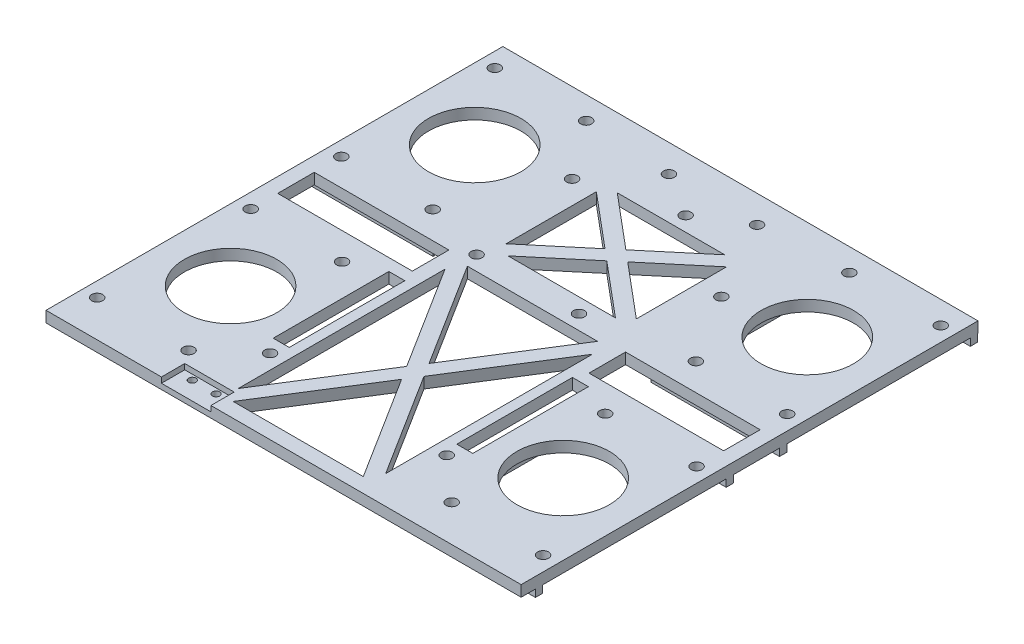
SolidWorks part; units mm, degrees
ref_plane "Front Plane" through (0, 0, 0) normal (0, 0, 1) x (1, 0, 0)
ref_plane "Top Plane" through (0, 0, 0) normal (0, 1, 0) x (1, 0, 0)
ref_plane "Right Plane" through (0, 0, 0) normal (1, 0, 0) x (0, 0, -1)
sketch "Sketch1" plane through (0, 0, 0) normal (0, 1, 0) x (1, 0, 0)
  line L1 (-65, 62.5) -> (65, 62.5)
  line L2 (-65, 62.5) -> (-65, -62.5)
  line L3 (-65, -62.5) -> (65, -62.5)
  line L4 (65, 62.5) -> (65, -62.5)
  line L5 (-65, 62.5) -> (65, -62.5) construction
  line L6 (-65, -62.5) -> (65, 62.5) construction
  point P0 (0, 0)
  dimension "D1" = 130
  dimension "D2" = 125
extrude "Boss-Extrude1" add sketch "Sketch1" along normal blind 5
sketch "Sketch2" plane through (0, 5, 0) normal (0, 1, 0) x (1, 0, 0)
  line L1 (-65, -62.5) -> (65, -62.5) construction
  line L2 (-65, 62.5) -> (-65, -62.5) construction
  circle A0 centre (-61, -52.5) radius 1.5
  circle A1 centre (-36, -52.5) radius 1.5
  circle A2 centre (-36, -10.5) radius 1.5
  circle A3 centre (-61, -10.5) radius 1.5
  circle A4 centre (-45.5, -31.5) radius 12.65
  dimension "D2" = 25.3
  dimension "D7" = 3
  dimension "D8" = 3
  dimension "D9" = 3
  dimension "D10" = 3
  dimension "D1" = 19.5
  dimension "D3" = 31
  dimension "D4" = 4
  dimension "D5" = 10
  dimension "D6" = 10
  dimension "D11" = 4
  dimension "D12" = 42
  dimension "D13" = 42
  dimension "D14" = 25
  dimension "D15" = 25
extrude "Cut-Extrude1" cut sketch "Sketch2" against normal blind 10
ref_plane "Plane1" through (0, 0, 0) normal (-1, 0, 0) x (0, 0, 1)
ref_plane "Plane2" through (0, 0, 0) normal (0, 0, 1) x (1, 0, 0)
mirror "Mirror3" about plane through (0, 0, 0) normal (-1, 0, 0) of "Cut-Extrude1"
sketch "Sketch4" plane through (0, 5, 0) normal (0, 1, 0) x (1, 0, 0)
  line L0 (0, 62.5) -> (0, 47.5) construction
  line L1 (65, 62.5) -> (-65, 62.5) construction
  line L2 (-12.0498, 55) -> (12.0498, 55) construction
  circle A0 centre (0, 47.5) radius 1.5
  circle A1 centre (12.0498, 55) radius 1.5
  circle A2 centre (-12.0498, 55) radius 1.5
  point P9 (0, 55)
  dimension "D2" = 3
  dimension "D3" = 3
  dimension "D4" = 3
  dimension "D1" = 15
  dimension "D5" = 24.0996
extrude "Cut-Extrude3" cut sketch "Sketch4" against normal blind 10
sketch "Sketch5" plane through (0, 0, 0) normal (0, -1, 0) x (1, 0, 0)
  line L0 (-58.15, 31.5) -> (-65, 31.5) construction
  line L1 (-65, -62.5) -> (-65, 62.5) construction
  line L2 (-65, 56.6) -> (-65, 6.4)
  line L3 (-65, 56.6) -> (-31.8, 56.6)
  line L4 (-31.8, 56.6) -> (-31.8, 6.4)
  line L5 (-31.8, 6.4) -> (-65, 6.4)
  line L6 (-65, 58.6) -> (-29.8, 58.6)
  line L7 (-29.8, 58.6) -> (-29.8, 4.4)
  line L8 (-29.8, 4.4) -> (-65, 4.4)
  line L9 (-65, 4.4) -> (-65, 6.4)
  line L10 (-65, 58.6) -> (-65, 56.6)
  circle A0 centre (-45.5, 31.5) radius 12.65 construction
  point P10 (-65, 31.5)
  line M39 (-65, 62.5) -> (-65, -62.5)
  dimension "D1" = 50.2
  dimension "D2" = 33.2
  dimension "D3" = 2
  dimension "D4" = 2
  dimension "D5" = 2
extrude "Boss-Extrude2" add sketch "Sketch5" along normal blind 2 contours L8 L7 L6 L3 L4 L5 M39 region at (-64.3537, 0, 57.6)
mirror "Mirror5" about plane through (0, 0, 0) normal (-1, 0, 0) of "Boss-Extrude2"
ref_plane "Plane3" through (0, 0, 0) normal (0, 0, 1) x (1, 0, 0)
ref_plane "Plane4" through (0, 0, -1.9) normal (0, 0, 1) x (1, 0, 0)
mirror "Mirror7" about plane through (0, 0, -1.9) normal (0, 0, 1) of "Mirror5", "Boss-Extrude2", "Mirror3"
ref_plane "Plane5" through (0, 0, 0) normal (0, -1, 0) x (-1, 0, 0)
sketch "Sketch10" plane through (0, 0, 0) normal (0, -1, 0) x (-1, 0, 0)
  circle A0 centre (-24.17, -42.03) radius 1.5
  circle A1 centre (24.17, -42.03) radius 1.5
  circle A2 centre (-8.73, 9.6) radius 1.5
  circle A3 centre (19.29, 9.6) radius 1.5
  circle A4 centre (-24.17, 33.11) radius 1.5
  circle A5 centre (24.17, 40.6) radius 1.5
  dimension "D1" = 3
  dimension "D6" = 3
  dimension "D7" = 3
  dimension "D10" = 3
  dimension "D11" = 3
  dimension "D12" = 3
extrude "Cut-Extrude8" cut sketch "Sketch10" against normal through all
sketch "Sketch11" plane through (0, 0, 0) normal (0, -1, 0) x (1, 0, 0)
  circle A0 centre (-12.0498, -55) radius 2.65
  circle A1 centre (0, -47.5) radius 2.65
  circle A2 centre (12.0498, -55) radius 2.65
  circle A3 centre (-24.17, -40.6) radius 2.65
  circle A4 centre (24.17, -33.11) radius 2.65
  circle A5 centre (8.73, -9.6) radius 2.65
  circle A6 centre (-19.29, -9.6) radius 2.65
  circle A7 centre (-24.17, 42.03) radius 2.65
  circle A8 centre (24.17, 42.03) radius 2.65
  circle A9 centre (-61, -14.3) radius 2.65
  circle A10 centre (-36, -14.3) radius 2.65
  circle A11 centre (-61, -56.3) radius 2.65
  circle A12 centre (-36, -56.3) radius 2.65
  circle A13 centre (36, -56.3) radius 2.65
  circle A14 centre (61, -56.3) radius 2.65
  circle A15 centre (36, -14.3) radius 2.65
  circle A16 centre (61, -14.3) radius 2.65
  circle A17 centre (36, 10.5) radius 2.65
  circle A18 centre (61, 10.5) radius 2.65
  circle A19 centre (61, 52.5) radius 2.65
  circle A20 centre (36, 52.5) radius 2.65
  circle A21 centre (-36, 52.5) radius 2.65
  circle A22 centre (-36, 10.5) radius 2.65
  circle A23 centre (-61, 10.5) radius 2.65
  circle A24 centre (-61, 52.5) radius 2.65
  dimension "D1" = 5.3
  dimension "D2" = 5.3
  dimension "D3" = 5.3
  dimension "D4" = 5.3
  dimension "D5" = 5.3
  dimension "D6" = 5.3
  dimension "D7" = 5.3
  dimension "D8" = 5.3
  dimension "D9" = 5.3
  dimension "D10" = 5.3
  dimension "D11" = 5.3
  dimension "D12" = 5.3
  dimension "D13" = 5.3
  dimension "D14" = 5.3
  dimension "D15" = 5.3
  dimension "D16" = 5.3
  dimension "D17" = 5.3
  dimension "D18" = 5.3
  dimension "D19" = 5.3
  dimension "D20" = 5.3
  dimension "D21" = 5.3
  dimension "D22" = 5.3
  dimension "D23" = 5.3
  dimension "D24" = 5.3
  dimension "D25" = 5.3
extrude "Cut-Extrude9" cut sketch "Sketch11" against normal blind 0.5
sketch "Sketch12" plane through (0, 5, 0) normal (0, 1, 0) x (1, 0, 0)
  line L0 (-65, -62.5) -> (65, -62.5) construction
  line L1 (-20.17, 5.6) -> (20.17, 5.6)
  line L2 (-20.17, 5.6) -> (-20.17, -58.5)
  line L3 (-20.17, -58.5) -> (20.17, -58.5)
  line L4 (20.17, 5.6) -> (20.17, -58.5)
  line L5 (-20.17, 5.6) -> (20.17, -58.5) construction
  line L6 (-20.17, -58.5) -> (20.17, 5.6) construction
  line L7 (-17.8069, 5.6) -> (0, -22.6951)
  line L8 (20.17, -54.7451) -> (2.3631, -26.45)
  line L9 (2.3631, -26.45) -> (20.17, 1.8451)
  line L10 (0, -22.6951) -> (17.8069, 5.6)
  line L11 (-20.17, 1.8451) -> (-2.3631, -26.45)
  line L12 (-2.3631, -26.45) -> (-20.17, -54.7451)
  line L13 (-17.8069, -58.5) -> (0, -30.2049)
  line L14 (0, -30.2049) -> (17.8069, -58.5)
  circle A0 centre (-19.29, 9.6) radius 1.5 construction
  circle A1 centre (-24.17, -42.03) radius 1.5 construction
  circle A2 centre (24.17, -42.03) radius 1.5 construction
  dimension "D2" = 4
  dimension "D3" = 4
  dimension "D1" = 4
  dimension "D4" = 4
  dimension "D5" = 2
  dimension "D6" = 2
  dimension "D7" = 2
  dimension "D8" = 2
extrude "Cut-Extrude10" cut sketch "Sketch12" against normal through all contours L12 L11 L2 | L7 L10 L1 | L9 L8 L4 | L14 L13 L3 region at (0, 5, 3.8317) region at (-14.2344, 5, 26.45) region at (14.2344, 5, 26.45) region at (0, 5, 49.0683)
sketch "Sketch13" plane through (0, 5, 0) normal (0, 1, 0) x (1, 0, 0)
  line L0 (-61, 14.3) -> (-61, -10.5) construction
  line L1 (-61, 1.9) -> (-61, -3.1)
  line L2 (-61, -3.1) -> (-24.17, -3.1)
  line L3 (-24.17, -3.1) -> (-24.17, 6.9)
  line L4 (-24.17, 6.9) -> (-61, 6.9)
  line L5 (-61, 6.9) -> (-61, 1.9)
  line L6 (-20.17, 1.8451) -> (-20.17, -54.7451) construction
  dimension "D1" = 10
  dimension "D2" = 5
  dimension "D3" = 4
extrude "Cut-Extrude11" cut sketch "Sketch13" against normal through all
mirror "Mirror9" about plane through (0, 0, 0) normal (-1, 0, 0) of "Cut-Extrude11"
sketch "Sketch14" plane through (0, 5, 0) normal (0, 1, 0) x (1, 0, 0)
  line L0 (-17.8069, 43.5) -> (17.8069, 13.6) construction
  line L1 (-17.8069, 43.5) -> (17.8069, 43.5)
  line L2 (-17.8069, 43.5) -> (-17.8069, 13.6)
  line L3 (-17.8069, 13.6) -> (17.8069, 13.6)
  line L4 (17.8069, 43.5) -> (17.8069, 13.6)
  line L5 (-17.8069, 13.6) -> (17.8069, 43.5) construction
  line L6 (-17.8069, 40.8886) -> (-3.1104, 28.55)
  line L7 (-3.1104, 28.55) -> (-17.8069, 16.2114)
  line L8 (-14.6965, 13.6) -> (0, 25.9386)
  line L9 (0, 25.9386) -> (14.6965, 13.6)
  line L10 (17.8069, 16.2114) -> (3.1104, 28.55)
  line L11 (3.1104, 28.55) -> (17.8069, 40.8886)
  line L12 (14.6965, 43.5) -> (0, 31.1614)
  line L13 (0, 31.1614) -> (-14.6965, 43.5)
  circle A0 centre (0, 47.5) radius 1.5 construction
  circle A1 centre (8.73, 9.6) radius 1.5 construction
  dimension "D1" = 4
  dimension "D2" = 4
  dimension "D3" = 2
  dimension "D4" = 2
  dimension "D5" = 2
  dimension "D6" = 2
  dimension "D7" = 2
  dimension "D8" = 2
  dimension "D9" = 2
  dimension "D10" = 2
extrude "Cut-Extrude12" cut sketch "Sketch14" against normal through all contours L7 L6 L2 | L13 L12 L1 | L11 L10 L4 | L9 L8 L3 region at (0, 5, -39.3871) region at (-12.9081, 5, -28.55) region at (12.9081, 5, -28.55) region at (0, 5, -17.7129)
sketch "Sketch15" plane through (0, 5, 0) normal (0, 1, 0) x (1, 0, 0)
  line L1 (-63.5, 58.8) -> (-58.5, 58.8)
  line L2 (-63.5, 58.8) -> (-63.5, 53.8)
  line L3 (-63.5, 53.8) -> (-58.5, 53.8)
  line L4 (65, -62.5) -> (65, 62.5)
  line L5 (65, 62.5) -> (-65, 62.5)
  line L6 (-65, 62.5) -> (-65, -62.5)
  line L7 (-65, -62.5) -> (65, -62.5)
  line L8 (65, -62.5) -> (65, 62.5)
  line L9 (65, 62.5) -> (-65, 62.5)
  line L10 (-65, 62.5) -> (-65, -62.5)
  line L11 (-65, -62.5) -> (65, -62.5)
  line L12 (-58.5, 58.8) -> (-58.5, 53.8)
  line L13 (-63.5, 58.8) -> (-58.5, 53.8) construction
  line L14 (-63.5, 53.8) -> (-58.5, 58.8) construction
  line L15 (-38.5, 58.8) -> (-33.5, 58.8)
  line L16 (-38.5, 58.8) -> (-38.5, 53.8)
  line L17 (-38.5, 53.8) -> (-33.5, 53.8)
  line L18 (-33.5, 58.8) -> (-33.5, 53.8)
  line L19 (-38.5, 58.8) -> (-33.5, 53.8) construction
  line L20 (-38.5, 53.8) -> (-33.5, 58.8) construction
  line L21 (-14.5498, 57.5) -> (-9.5498, 57.5)
  line L22 (-14.5498, 57.5) -> (-14.5498, 52.5)
  line L23 (-14.5498, 52.5) -> (-9.5498, 52.5)
  line L24 (-9.5498, 57.5) -> (-9.5498, 52.5)
  line L25 (-14.5498, 57.5) -> (-9.5498, 52.5) construction
  line L26 (-14.5498, 52.5) -> (-9.5498, 57.5) construction
  line L27 (-2.5, 50) -> (2.5, 50)
  line L28 (-2.5, 50) -> (-2.5, 45)
  line L29 (-2.5, 45) -> (2.5, 45)
  line L30 (2.5, 50) -> (2.5, 45)
  line L31 (-2.5, 50) -> (2.5, 45) construction
  line L32 (-2.5, 45) -> (2.5, 50) construction
  line L33 (9.5498, 57.5) -> (14.5498, 57.5)
  line L34 (9.5498, 57.5) -> (9.5498, 52.5)
  line L35 (9.5498, 52.5) -> (14.5498, 52.5)
  line L36 (14.5498, 57.5) -> (14.5498, 52.5)
  line L37 (9.5498, 57.5) -> (14.5498, 52.5) construction
  line L38 (9.5498, 52.5) -> (14.5498, 57.5) construction
  line L39 (33.5, 58.8) -> (38.5, 58.8)
  line L40 (33.5, 58.8) -> (33.5, 53.8)
  line L41 (33.5, 53.8) -> (38.5, 53.8)
  line L42 (38.5, 58.8) -> (38.5, 53.8)
  line L43 (33.5, 58.8) -> (38.5, 53.8) construction
  line L44 (33.5, 53.8) -> (38.5, 58.8) construction
  line L45 (63.5, 58.8) -> (58.5, 58.8)
  line L46 (63.5, 58.8) -> (63.5, 53.8)
  line L47 (63.5, 53.8) -> (58.5, 53.8)
  line L48 (58.5, 58.8) -> (58.5, 53.8)
  line L49 (63.5, 58.8) -> (58.5, 53.8) construction
  line L50 (63.5, 53.8) -> (58.5, 58.8) construction
  line L51 (33.5, 16.8) -> (38.5, 16.8)
  line L52 (33.5, 16.8) -> (33.5, 11.8)
  line L53 (33.5, 11.8) -> (38.5, 11.8)
  line L54 (38.5, 16.8) -> (38.5, 11.8)
  line L55 (33.5, 16.8) -> (38.5, 11.8) construction
  line L56 (33.5, 11.8) -> (38.5, 16.8) construction
  line L57 (63.5, 16.8) -> (58.5, 16.8)
  line L58 (63.5, 16.8) -> (63.5, 11.8)
  line L59 (63.5, 11.8) -> (58.5, 11.8)
  line L60 (58.5, 16.8) -> (58.5, 11.8)
  line L61 (63.5, 16.8) -> (58.5, 11.8) construction
  line L62 (63.5, 11.8) -> (58.5, 16.8) construction
  line L63 (21.67, 35.61) -> (26.67, 35.61)
  line L64 (21.67, 35.61) -> (21.67, 30.61)
  line L65 (21.67, 30.61) -> (26.67, 30.61)
  line L66 (26.67, 35.61) -> (26.67, 30.61)
  line L67 (21.67, 35.61) -> (26.67, 30.61) construction
  line L68 (21.67, 30.61) -> (26.67, 35.61) construction
  line L69 (33.5, -8) -> (38.5, -8)
  line L70 (33.5, -8) -> (33.5, -13)
  line L71 (33.5, -13) -> (38.5, -13)
  line L72 (38.5, -8) -> (38.5, -13)
  line L73 (33.5, -8) -> (38.5, -13) construction
  line L74 (33.5, -13) -> (38.5, -8) construction
  line L75 (63.5, -8) -> (58.5, -8)
  line L76 (63.5, -8) -> (63.5, -13)
  line L77 (63.5, -13) -> (58.5, -13)
  line L78 (58.5, -8) -> (58.5, -13)
  line L79 (63.5, -8) -> (58.5, -13) construction
  line L80 (63.5, -13) -> (58.5, -8) construction
  line L81 (21.67, -39.53) -> (26.67, -39.53)
  line L82 (21.67, -39.53) -> (21.67, -44.53)
  line L83 (21.67, -44.53) -> (26.67, -44.53)
  line L84 (26.67, -39.53) -> (26.67, -44.53)
  line L85 (21.67, -39.53) -> (26.67, -44.53) construction
  line L86 (21.67, -44.53) -> (26.67, -39.53) construction
  line L87 (38.5, -50) -> (33.5, -50)
  line L88 (38.5, -50) -> (38.5, -55)
  line L89 (38.5, -55) -> (33.5, -55)
  line L90 (33.5, -50) -> (33.5, -55)
  line L91 (38.5, -50) -> (33.5, -55) construction
  line L92 (38.5, -55) -> (33.5, -50) construction
  line L93 (63.5, -50) -> (58.5, -50)
  line L94 (63.5, -50) -> (63.5, -55)
  line L95 (63.5, -55) -> (58.5, -55)
  line L96 (58.5, -50) -> (58.5, -55)
  line L97 (63.5, -50) -> (58.5, -55) construction
  line L98 (63.5, -55) -> (58.5, -50) construction
  line L99 (-26.67, -39.53) -> (-21.67, -39.53)
  line L100 (-26.67, -39.53) -> (-26.67, -44.53)
  line L101 (-26.67, -44.53) -> (-21.67, -44.53)
  line L102 (-21.67, -39.53) -> (-21.67, -44.53)
  line L103 (-26.67, -39.53) -> (-21.67, -44.53) construction
  line L104 (-26.67, -44.53) -> (-21.67, -39.53) construction
  line L105 (-38.5, -50) -> (-33.5, -50)
  line L106 (-38.5, -50) -> (-38.5, -55)
  line L107 (-38.5, -55) -> (-33.5, -55)
  line L108 (-33.5, -50) -> (-33.5, -55)
  line L109 (-38.5, -50) -> (-33.5, -55) construction
  line L110 (-38.5, -55) -> (-33.5, -50) construction
  line L111 (-38.5, -8) -> (-33.5, -8)
  line L112 (-38.5, -8) -> (-38.5, -13)
  line L113 (-38.5, -13) -> (-33.5, -13)
  line L114 (-33.5, -8) -> (-33.5, -13)
  line L115 (-38.5, -8) -> (-33.5, -13) construction
  line L116 (-38.5, -13) -> (-33.5, -8) construction
  line L117 (6.23, 12.1) -> (11.23, 12.1)
  line L118 (6.23, 12.1) -> (6.23, 7.1)
  line L119 (6.23, 7.1) -> (11.23, 7.1)
  line L120 (11.23, 12.1) -> (11.23, 7.1)
  line L121 (6.23, 12.1) -> (11.23, 7.1) construction
  line L122 (6.23, 7.1) -> (11.23, 12.1) construction
  line L123 (-21.79, 12.1) -> (-16.79, 12.1)
  line L124 (-21.79, 12.1) -> (-21.79, 7.1)
  line L125 (-21.79, 7.1) -> (-16.79, 7.1)
  line L126 (-16.79, 12.1) -> (-16.79, 7.1)
  line L127 (-21.79, 12.1) -> (-16.79, 7.1) construction
  line L128 (-21.79, 7.1) -> (-16.79, 12.1) construction
  line L129 (-26.67, 43.1) -> (-21.67, 43.1)
  line L130 (-26.67, 43.1) -> (-26.67, 38.1)
  line L131 (-26.67, 38.1) -> (-21.67, 38.1)
  line L132 (-21.67, 43.1) -> (-21.67, 38.1)
  line L133 (-26.67, 43.1) -> (-21.67, 38.1) construction
  line L134 (-26.67, 38.1) -> (-21.67, 43.1) construction
  line L135 (-63.5, 16.8) -> (-58.5, 16.8)
  line L136 (-63.5, 16.8) -> (-63.5, 11.8)
  line L137 (-63.5, 11.8) -> (-58.5, 11.8)
  line L138 (-58.5, 16.8) -> (-58.5, 11.8)
  line L139 (-63.5, 16.8) -> (-58.5, 11.8) construction
  line L140 (-63.5, 11.8) -> (-58.5, 16.8) construction
  line L141 (-38.5, 16.8) -> (-33.5, 16.8)
  line L142 (-38.5, 16.8) -> (-38.5, 11.8)
  line L143 (-38.5, 11.8) -> (-33.5, 11.8)
  line L144 (-33.5, 16.8) -> (-33.5, 11.8)
  line L145 (-38.5, 16.8) -> (-33.5, 11.8) construction
  line L146 (-38.5, 11.8) -> (-33.5, 16.8) construction
  line L147 (-63.5, -8) -> (-58.5, -8)
  line L148 (-63.5, -8) -> (-63.5, -13)
  line L149 (-63.5, -13) -> (-58.5, -13)
  line L150 (-58.5, -8) -> (-58.5, -13)
  line L151 (-63.5, -8) -> (-58.5, -13) construction
  line L152 (-63.5, -13) -> (-58.5, -8) construction
  line L153 (-63.5, -50) -> (-58.5, -50)
  line L154 (-63.5, -50) -> (-63.5, -55)
  line L155 (-63.5, -55) -> (-58.5, -55)
  line L156 (-58.5, -50) -> (-58.5, -55)
  line L157 (-63.5, -50) -> (-58.5, -55) construction
  line L158 (-63.5, -55) -> (-58.5, -50) construction
  circle A0 centre (-61, 56.3) radius 1.5 construction
  circle A1 centre (-36, 56.3) radius 1.5 construction
  circle A2 centre (-12.0498, 55) radius 1.5 construction
  circle A3 centre (0, 47.5) radius 1.5 construction
  circle A4 centre (12.0498, 55) radius 1.5 construction
  circle A5 centre (36, 56.3) radius 1.5 construction
  circle A6 centre (61, 56.3) radius 1.5 construction
  circle A7 centre (24.17, 33.11) radius 1.5 construction
  circle A8 centre (36, 14.3) radius 1.5 construction
  circle A9 centre (61, 14.3) radius 1.5 construction
  circle A10 centre (-24.17, 40.6) radius 1.5 construction
  circle A11 centre (-61, 14.3) radius 1.5 construction
  circle A12 centre (-36, 14.3) radius 1.5 construction
  circle A13 centre (-19.29, 9.6) radius 1.5 construction
  circle A14 centre (8.73, 9.6) radius 1.5 construction
  circle A15 centre (-61, -10.5) radius 1.5 construction
  circle A16 centre (-36, -10.5) radius 1.5 construction
  circle A17 centre (36, -10.5) radius 1.5 construction
  circle A18 centre (61, -10.5) radius 1.5 construction
  circle A19 centre (61, -52.5) radius 1.5 construction
  circle A20 centre (36, -52.5) radius 1.5 construction
  circle A21 centre (24.17, -42.03) radius 1.5 construction
  circle A22 centre (-24.17, -42.03) radius 1.5 construction
  circle A23 centre (-36, -52.5) radius 1.5 construction
  circle A24 centre (-61, -52.5) radius 1.5 construction
  point P2 (-61, 56.3)
  point P12 (-36, 56.3)
  point P20 (-12.0498, 55)
  point P26 (0, 47.5)
  point P32 (12.0498, 55)
  point P38 (36, 56.3)
  point P44 (61, 56.3)
  point P50 (36, 14.3)
  point P56 (61, 14.3)
  point P62 (24.17, 33.11)
  point P84 (36, -10.5)
  point P90 (61, -10.5)
  point P96 (24.17, -42.03)
  point P102 (36, -52.5)
  point P108 (61, -52.5)
  point P114 (-24.17, -42.03)
  point P120 (-36, -52.5)
  point P126 (-36, -10.5)
  point P132 (8.73, 9.6)
  point P138 (-19.29, 9.6)
  point P144 (-24.17, 40.6)
  point P150 (-61, 14.3)
  point P156 (-36, 14.3)
  point P162 (-61, -10.5)
  point P168 (-61, -52.5)
  dimension "D2" = 2.5
  dimension "D3" = 2.5
  dimension "D4" = 2.5
  dimension "D5" = 2.5
  dimension "D6" = 2.5
  dimension "D7" = 2.5
  dimension "D8" = 2.5
  dimension "D9" = 2.5
  dimension "D10" = 2.5
  dimension "D11" = 2.5
  dimension "D12" = 2.5
  dimension "D13" = 2.5
  dimension "D15" = 2.5
  dimension "D16" = 2.5
  dimension "D17" = 2.5
  dimension "D18" = 2.5
  dimension "D19" = 2.5
  dimension "D20" = 2.5
  dimension "D21" = 2.5
  dimension "D22" = 2.5
  dimension "D23" = 2.5
  dimension "D24" = 2.5
  dimension "D25" = 2.5
  dimension "D26" = 2.5
  dimension "D27" = 2.5
  dimension "D28" = 2.5
  dimension "D29" = 2.5
  dimension "D30" = 2.5
  dimension "D31" = 2.5
  dimension "D32" = 2.5
  dimension "D33" = 2.5
  dimension "D34" = 2.5
  dimension "D35" = 2.5
  dimension "D36" = 2.5
  dimension "D37" = 2.5
  dimension "D38" = 2.5
  dimension "D39" = 2.5
  dimension "D40" = 2.5
  dimension "D41" = 2.5
  dimension "D42" = 2.5
  dimension "D43" = 2.5
  dimension "D44" = 2.5
  dimension "D45" = 2.5
  dimension "D46" = 2.5
  dimension "D47" = 2.5
  dimension "D48" = 2.5
  dimension "D49" = 2.5
  dimension "D14" = 2.5
  dimension "D1" = 0
extrude "Cut-Extrude14" cut sketch "Sketch15" against normal blind 2
ref_plane "Plane6" through (0, 13, 0) normal (0, 1, 0) x (1, 0, 0)
sketch "Sketch17" plane through (0, 13, 0) normal (0, 1, 0) x (1, 0, 0)
  line L1 (-68.0587, 64.2777) -> (69.5711, 64.2777)
  line L2 (-68.0587, 64.2777) -> (-68.0587, -66.7984)
  line L3 (-68.0587, -66.7984) -> (69.5711, -66.7984)
  line L4 (69.5711, 64.2777) -> (69.5711, -66.7984)
extrude "Cut-Extrude15" cut sketch "Sketch17" against normal blind 2 from surface starting at face at (-61, 5, -15.8)
sketch "Sketch18" plane through (0, 3, 0) normal (0, 1, 0) x (1, 0, 0)
  line L0 (-65, -62.5) -> (65, -62.5) construction
  line L1 (-33.412, -56.1297) -> (-19.8846, -56.1297)
  line L2 (-33.412, -56.1297) -> (-33.412, -62.5)
  line L3 (-33.412, -62.5) -> (-19.8846, -62.5)
  line L4 (-19.8846, -56.1297) -> (-19.8846, -62.5)
extrude "Cut-Extrude16" cut sketch "Sketch18" against normal blind 1.5
sketch "Sketch19" plane through (0, 1.5, 0) normal (0, 1, 0) x (1, 0, 0)
  circle A0 centre (-23.4201, -57.55) radius 1
  circle A1 centre (-29.9201, -57.55) radius 1
extrude "Cut-Extrude17" cut sketch "Sketch19" against normal blind 5
sketch "Sketch20" plane through (0, 0, 0) normal (0, -1, 0) x (1, 0, 0)
  line L1 (-32.8112, 59.7055) -> (-26.1535, 59.7055)
  line L2 (-32.8112, 59.7055) -> (-32.8112, 55.2822)
  line L3 (-32.8112, 55.2822) -> (-26.1535, 55.2822)
  line L4 (-26.1535, 59.7055) -> (-26.1535, 55.2822)
extrude "Cut-Extrude18" cut sketch "Sketch20" along normal up to surface (2 mm away) up to face at (-44.392, -2, 36.71)
sketch "Sketch21" plane through (0, 0, 0) normal (0, -1, 0) x (-1, 0, 0)
  line L0 (-29.8, -58.6) -> (-29.8, -4.4) construction
  line L1 (-27.3, -6.4) -> (-22.9235, -6.4)
  line L2 (-27.3, -6.4) -> (-27.3, -38.03)
  line L3 (-27.3, -38.03) -> (-22.9235, -38.03)
  line L4 (-22.9235, -6.4) -> (-22.9235, -38.03)
  line L5 (22.92, -6.4) -> (27.3, -6.4)
  line L6 (22.92, -6.4) -> (22.92, -38.03)
  line L7 (22.92, -38.03) -> (27.3, -38.03)
  line L8 (27.3, -6.4) -> (27.3, -38.03)
  line L11 (29.8, -55.2822) -> (29.8, -4.4) construction
  line L12 (-20.17, 1.8451) -> (-20.17, -54.7451) construction
  line L13 (20.17, 1.8451) -> (20.17, -54.7451) construction
  line L14 (31.8, -6.4) -> (65, -6.4) construction
  circle A0 centre (-24.17, -42.03) radius 2.65 construction
  dimension "D5" = 4
  dimension "D1" = 2.5
  dimension "D2" = 2.5
  dimension "D3" = 2.7535
  dimension "D4" = 2.75
extrude "Cut-Extrude19" cut sketch "Sketch21" against normal blind 7.4
